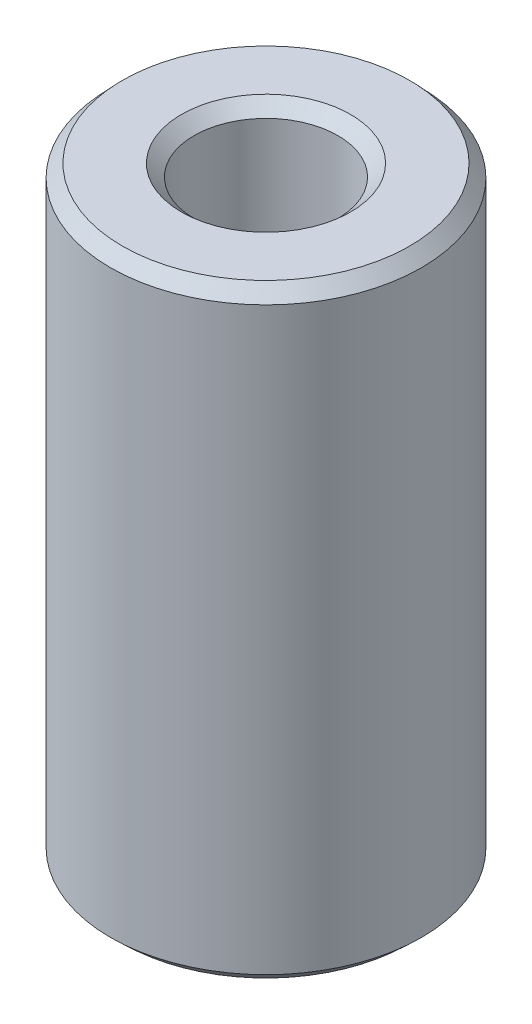
SolidWorks part; units mm, degrees
ref_plane "Front Plane" through (0, 0, 0) normal (0, 0, 1) x (1, 0, 0)
ref_plane "Top Plane" through (0, 0, 0) normal (0, 1, 0) x (1, 0, 0)
ref_plane "Right Plane" through (0, 0, 0) normal (1, 0, 0) x (0, 0, -1)
sketch "Sketch1" plane through (0, 0, 0) normal (0, 1, 0) x (1, 0, 0)
  circle A0 centre (0, 0) radius 15
  dimension "SLEEVE_OD" = 30
extrude "Boss-Extrude1" add sketch "Sketch1" along normal blind 58.3265
sketch "Sketch2" plane through (0, 0, 0) normal (0, 1, 0) x (1, 0, 0)
  circle A0 centre (0, 0) radius 6.9298
  dimension "BORE_D" = 13.8595
extrude "Cut-Extrude1" cut sketch "Sketch2" along normal through all
chamfer "Chamfer1" distance 1.2281 angle 43.12 4 edges at (0, 58.3265, 6.9298) (0, 0, 6.9298) (0, 0, 15) (0, 58.3265, 15) first distance on face at (0, 58.3265, 6.9298) first distance on face at (0, 0, 6.9298) first distance on face at (0, 58.3265, 15)
